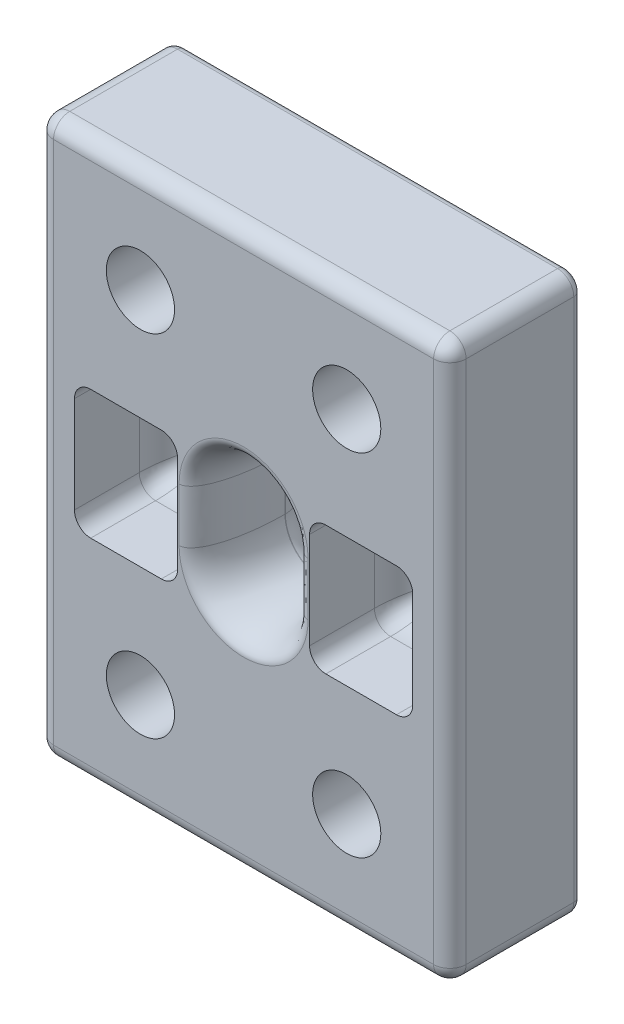
SolidWorks part; units mm, degrees
ref_plane "Front" through (0, 0, 0) normal (0, 0, 1) x (1, 0, 0)
ref_plane "Top" through (0, 0, 0) normal (0, 1, 0) x (1, 0, 0)
ref_plane "Right" through (0, 0, 0) normal (1, 0, 0) x (0, 0, -1)
sketch "Sketch1" plane through (0, 0, 0) normal (0, 0, 1) x (1, 0, 0)
  line L0 (0, 1.6424) -> (0, -1.6424) construction
  line L1 (-12.7, 17.145) -> (12.7, 17.145)
  line L2 (-12.7, 17.145) -> (-12.7, -17.145)
  line L3 (-12.7, -17.145) -> (12.7, -17.145)
  line L4 (12.7, 17.145) -> (12.7, -17.145)
  line L5 (-12.7, 17.145) -> (12.7, -17.145) construction
  line L6 (-12.7, -17.145) -> (12.7, 17.145) construction
  line L7 (-6.35, 10.795) -> (6.35, 10.795) construction
  line L8 (-6.35, 10.795) -> (-6.35, -10.795) construction
  line L9 (-6.35, -10.795) -> (6.35, -10.795) construction
  line L10 (6.35, 10.795) -> (6.35, -10.795) construction
  line L11 (-6.35, 10.795) -> (6.35, -10.795) construction
  line L12 (-6.35, -10.795) -> (6.35, 10.795) construction
  line L13 (2.3813, 1.6424) -> (2.3813, -1.6424)
  line L14 (-2.3813, 1.6424) -> (-2.3813, -1.6424)
  circle A0 centre (-6.35, 10.795) radius 2.1001
  circle A1 centre (6.35, 10.795) radius 2.1001
  circle A2 centre (6.35, -10.795) radius 2.1001
  circle A3 centre (-6.35, -10.795) radius 2.1001
  arc A4 (2.3813, 1.6424) -> (-2.3813, 1.6424) centre (0, 1.6424) ccw
  arc A5 (-2.3813, -1.6424) -> (2.3813, -1.6424) centre (0, -1.6424) ccw
  point P0 (0, 0)
  point P5 (0, 0)
  point P16 (0, 0)
  point P18 (0, 0)
  point P25 (0, 0)
  dimension "D5" = 4.2001
  dimension "D6" = 2.3813
  dimension "D1" = 34.29
  dimension "D2" = 25.4
  dimension "D3" = 12.7
  dimension "D4" = 21.59
  dimension "D7" = 3.2847
extrude "Boss-Extrude1" add sketch "Sketch1" along normal blind 8.1313
sketch "Sketch3" plane through (0, 0, 8.1313) normal (0, 0, 1) x (1, 0, 0)
  line L0 (-12.7, 0) -> (-7.239, 0) construction
  line L3 (-12.7, 17.145) -> (-12.7, -17.145) construction
  line L4 (-10.414, 3.9688) -> (-4.064, 3.9688)
  line L5 (-10.414, 3.9688) -> (-10.414, -3.9688)
  line L6 (-10.414, -3.9688) -> (-4.064, -3.9687)
  line L7 (-4.064, 3.9688) -> (-4.064, -3.9687)
  line L8 (-10.414, 3.9688) -> (-4.064, -3.9687) construction
  line L9 (-10.414, -3.9688) -> (-4.064, 3.9688) construction
  line L10 (4.064, 3.9688) -> (10.414, 3.9688)
  line L11 (4.064, 3.9688) -> (4.064, -3.9687)
  line L12 (4.064, -3.9687) -> (10.414, -3.9687)
  line L13 (10.414, 3.9688) -> (10.414, -3.9687)
  line L14 (4.064, 3.9688) -> (10.414, -3.9687) construction
  line L15 (4.064, -3.9687) -> (10.414, 3.9688) construction
  line L16 (-7.239, 0) -> (7.239, 0) construction
  line L17 (7.239, 0) -> (12.7, 0) construction
  line L18 (12.7, -17.145) -> (12.7, 17.145) construction
  point P6 (-7.239, 0)
  point P11 (7.239, 0)
  dimension "D1" = 6.35
  dimension "D2" = 7.9375
  dimension "D3" = 2.286
extrude "Cut-Extrude1" cut sketch "Sketch3" against normal blind 6.5311
sketch "Sketch4" plane through (0, 0, 0) normal (0, 0, -1) x (-1, 0, 0)
  line L1 (-6.35, 5.8298) -> (-2.05, 8.3124)
  line L2 (-2.05, 8.3124) -> (-2.05, 13.2776)
  line L3 (-2.05, 13.2776) -> (-6.35, 15.7602)
  line L4 (-6.35, 15.7602) -> (-10.65, 13.2776)
  line L5 (-10.65, 13.2776) -> (-10.65, 8.3124)
  line L6 (-10.65, 8.3124) -> (-6.35, 5.8298)
  line L7 (6.35, 5.8298) -> (10.65, 8.3124)
  line L8 (10.65, 8.3124) -> (10.65, 13.2776)
  line L9 (10.65, 13.2776) -> (6.35, 15.7602)
  line L10 (6.35, 15.7602) -> (2.05, 13.2776)
  line L11 (2.05, 13.2776) -> (2.05, 8.3124)
  line L12 (2.05, 8.3124) -> (6.35, 5.8298)
  line L13 (6.35, -15.7602) -> (10.65, -13.2776)
  line L14 (10.65, -13.2776) -> (10.65, -8.3124)
  line L15 (10.65, -8.3124) -> (6.35, -5.8298)
  line L16 (6.35, -5.8298) -> (2.05, -8.3124)
  line L17 (2.05, -8.3124) -> (2.05, -13.2776)
  line L18 (2.05, -13.2776) -> (6.35, -15.7602)
  line L19 (-6.35, -15.7602) -> (-2.05, -13.2776)
  line L20 (-2.05, -13.2776) -> (-2.05, -8.3124)
  line L21 (-2.05, -8.3124) -> (-6.35, -5.8298)
  line L22 (-6.35, -5.8298) -> (-10.65, -8.3124)
  line L23 (-10.65, -8.3124) -> (-10.65, -13.2776)
  line L24 (-10.65, -13.2776) -> (-6.35, -15.7602)
  circle A0 centre (-6.35, 10.795) radius 4.3 construction
  circle A1 centre (6.35, 10.795) radius 4.3 construction
  circle A2 centre (6.35, -10.795) radius 4.3 construction
  circle A3 centre (-6.35, -10.795) radius 4.3 construction
  circle M25 centre (6.35, -10.795) radius 2.1001
  circle M26 centre (-6.35, -10.795) radius 2.1001
  circle M27 centre (-6.35, 10.795) radius 2.1001
  circle M28 centre (6.35, 10.795) radius 2.1001
  dimension "D1" = 8.5999
extrude "Cut-Extrude2" cut sketch "Sketch4" against normal blind 4 contours L5 L6 L1 L2 L3 L4 M27 | L11 L12 L7 L8 L9 L10 M28 | L17 L18 L13 L14 L15 L16 M25 | L23 L24 L19 L20 L21 L22 M26 region at (8.4343, 7.1849, 0) region at (-4.2657, 7.1849, 0) region at (-4.2657, -14.4051, 0) region at (8.4343, -14.4051, 0)
fillet "Fillet1" radius 3.175 4 edges at (0, 4.0236, 0) (2.3813, 0, 0) (0, -4.0236, 0) (-2.3813, 0, 0) second distance 6.35 tangent propagation no first distance on face at (0, 2.833, 4.0657) first distance on face at (2.3813, 0, 4.0657) first distance on face at (0, -2.833, 4.0657) first distance on face at (-2.3813, 0, 4.0657)
fillet "Fillet2" radius 0.4712 80 edges at (4.2, -7.0711, 4) (2.05, -10.795, 4) (4.2, -14.5189, 4) (2.05, -13.2776, 2) (4.2, -14.5189, 0) (8.5, -14.5189, 4) (6.35, -15.7602, 2) (8.5, -14.5189, 0) (8.5, -7.0711, 4) (10.65, -8.3124, 2) (10.65, -10.795, 4) (10.65, -13.2776, 2) (10.65, -10.795, 0) (-2.05, -10.795, 4) (-8.5, -14.5189, 4) (-8.5, -14.5189, 0) (-2.05, -13.2776, 2) (-4.2, -14.5189, 4) (-6.35, -15.7602, 2) (-4.2, -14.5189, 0) (-10.65, -13.2776, 2) (-10.65, -10.795, 4) (-10.65, -10.795, 0) (-10.65, -8.3124, 2) (-8.5, -7.0711, 4) (-4.2, -7.0711, 4) (-8.5, 7.0711, 4) (-10.65, 8.3124, 2) (-10.65, 10.795, 4) (-10.65, 10.795, 0) (-10.65, 13.2776, 2) (-8.5, 14.5189, 4) (-8.5, 14.5189, 0) (-6.35, 15.7602, 2) (-4.2, 14.5189, 4) (-4.2, 14.5189, 0) (-2.05, 13.2776, 2) (-2.05, 10.795, 4) (-4.2, 7.0711, 4) (8.5, 7.0711, 4) (8.5, 14.5189, 4) (8.5, 14.5189, 0) (10.65, 13.2776, 2) (10.65, 10.795, 4) (10.65, 8.3124, 2) (10.65, 10.795, 0) (4.2, 14.5189, 4) (6.35, 15.7602, 2) (4.2, 14.5189, 0) (2.05, 10.795, 4) (2.05, 13.2776, 2) (4.2, 7.0711, 4)
fillet "Fillet3" radius 1.5875 4 edges at (0, 4.0236, 8.1313) (0, -4.0236, 8.1313) (2.3813, 0, 8.1313) (-2.3813, 0, 8.1313) second distance 4.9291 tangent propagation no first distance on face at (-7.239, 0, 8.1313)
fillet "Fillet4" radius 2.54 8 edges at (-7.239, -3.9688, 1.6002) (-10.414, 0, 1.6002) (-7.239, 3.9688, 1.6002) (-4.064, 0, 1.6002) (7.239, -3.9687, 1.6002) (4.064, 0, 1.6002) (7.239, 3.9688, 1.6002) (10.414, 0, 1.6002)
fillet "Fillet5" radius 1 24 edges at (-4.8079, -3.2248, 2.3441) (-4.8079, 3.2248, 2.3441) (-9.6701, 3.2248, 2.3441) (-9.6701, -3.2248, 2.3441) (4.8079, -3.2248, 2.3441) (9.6701, -3.2248, 2.3441) (9.6701, 3.2248, 2.3441) (4.8079, 3.2248, 2.3441) (-4.064, -3.9687, 6.1358) (-4.064, 3.9688, 6.1358) (-10.414, 3.9688, 6.1358) (-10.414, -3.9688, 6.1358) (4.064, -3.9687, 6.1358) (10.414, -3.9687, 6.1358) (10.414, 3.9688, 6.1358) (4.064, 3.9688, 6.1358) (-12.7, -17.145, 4.0657) (12.7, -17.145, 4.0657) (12.7, 17.145, 4.0657) (-12.7, 17.145, 4.0657) (-12.7, 0, 8.1313) (0, 17.145, 8.1313) (12.7, 0, 8.1313) (0, -17.145, 8.1313)
fillet "Fillet7" radius 0.5001 8 edges at (12.4071, -16.8521, 0) (0, -17.145, 0) (-12.4071, -16.8521, 0) (-12.7, 0, 0) (-12.4071, 16.8521, 0) (0, 17.145, 0) (12.4071, 16.8521, 0) (12.7, 0, 0)
